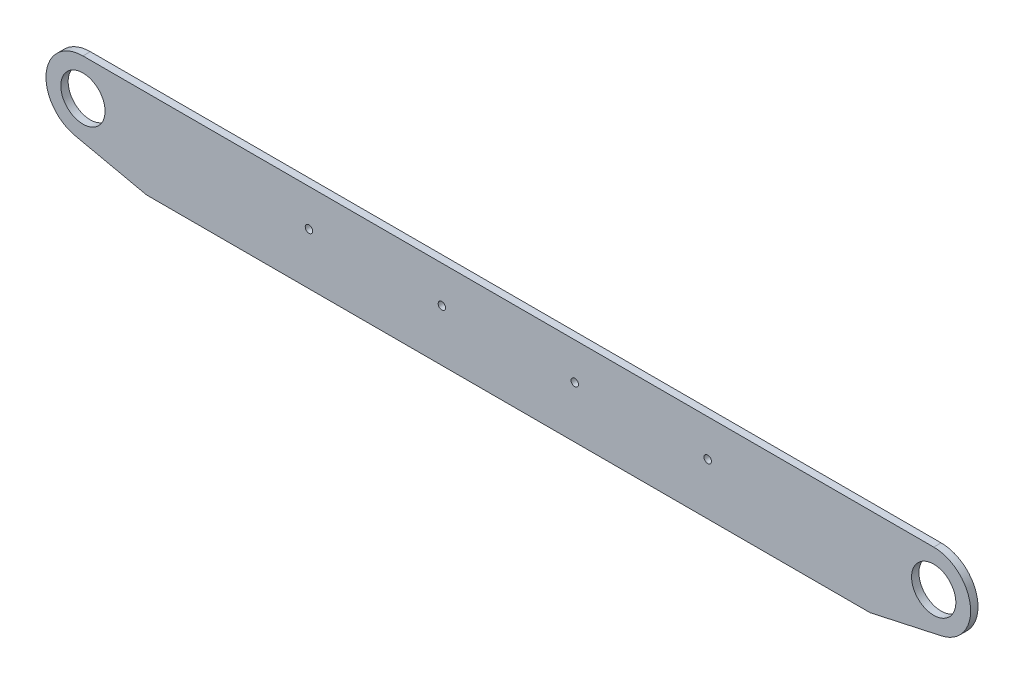
SolidWorks part; units mm, degrees
material "6061 Alloy"
ref_plane "Front Plane" through (0, 0, 0) normal (0, 0, 1) x (1, 0, 0)
ref_plane "Top Plane" through (0, 0, 0) normal (0, 1, 0) x (1, 0, 0)
ref_plane "Right Plane" through (0, 0, 0) normal (1, 0, 0) x (0, 0, -1)
sketch "Sketch1" plane through (0, 0, 457.2) normal (0, 0, 1) x (1, 0, 0)
  line L0 (311.15, 0) -> (311.15, 609.6) construction
  line L1 (-311.15, 609.6) -> (311.15, 609.6)
  line L2 (-311.15, 609.6) -> (-311.15, 533.4)
  line L3 (-311.15, 533.4) -> (311.15, 533.4)
  line L4 (311.15, 609.6) -> (311.15, 533.4)
  line L6 (311.15, 114.3) -> (-311.15, 114.3) construction
  dimension "D1" = 419.1
extrude "Boss-Extrude1" add sketch "Sketch1" along normal blind 6.35
sketch "Sketch2" plane through (0, 0, 463.55) normal (0, 0, 1) x (1, 0, 0)
  point P0 (171.45, 577.85)
hole_wizard "1/4 (0.25) Diameter Hole1" positions "Sketch2" profile "Sketch3" hole size "1/4" standard "ANSI Inch" end condition through all
sketch "Sketch3" plane through (171.45, 577.85, 463.55) normal (1, 0, 0) x (0, -1, 0)
  line L0 (0, 0) -> (0, 6.35)
  line L1 (0, 6.35) -> (3.175, 6.35)
  line L2 (3.175, 6.35) -> (3.175, 0)
  line L5 (3.175, 0) -> (0, 0)
  line L11 (0, -6.35) -> (0, 107.95) construction
  dimension "Thru Hole Dia." = 6.35
  dimension "Thru Hole Depth" = 6.35
pattern_linear "LPattern1" count 4 spacing 114.3 along (-1, 0, 0) of "1/4 (0.25) Diameter Hole1"
sketch "Sketch4" plane through (0, 0, 463.55) normal (0, 0, 1) x (1, 0, 0)
  line L0 (311.15, 533.4) -> (372.5878, 546.8327)
  line L1 (311.15, 609.6) -> (365.8062, 609.6)
  line L2 (311.15, 609.6) -> (311.15, 533.4)
  arc A0 (372.5878, 546.8327) -> (365.8062, 609.6) centre (365.8062, 577.85) ccw
  circle A1 centre (365.8062, 577.85) radius 19.05
  dimension "D1" = 63.5
  dimension "D2" = 38.1
extrude "Boss-Extrude3" add sketch "Sketch4" against normal up to surface (6.35 mm away) up to face at (60.325, 577.85, 457.2)
mirror "Mirror1" about plane through (0, 0, 0) normal (1, 0, 0) of "Boss-Extrude3"
